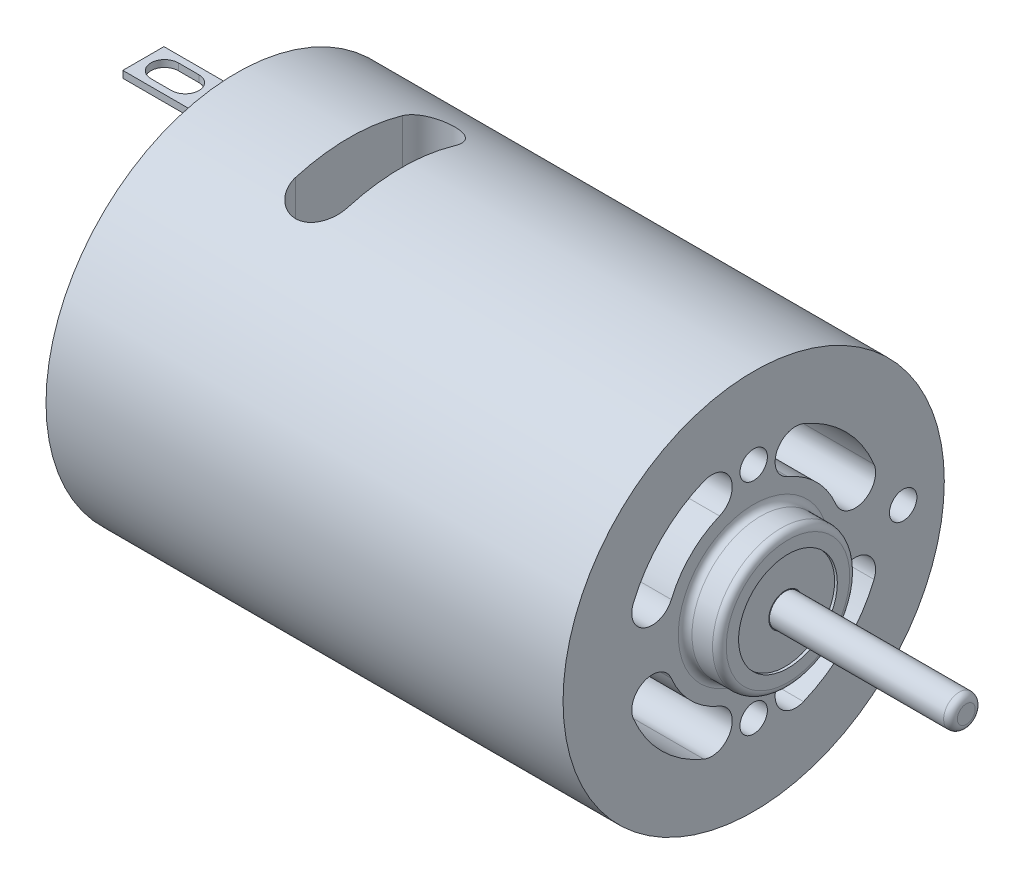
SolidWorks part; units mm, degrees
ref_plane "前视基准面" through (0, 0, 0) normal (0, 0, 1) x (1, 0, 0)
ref_plane "上视基准面" through (0, 0, 0) normal (0, 1, 0) x (1, 0, 0)
ref_plane "右视基准面" through (0, 0, 0) normal (1, 0, 0) x (0, 0, -1)
other "Configuration Table"
sketch "草图1" plane through (0, 0, 0) normal (1, 0, 0) x (0, 0, -1)
  circle A0 centre (0, 0) radius 13.9
  dimension "D1" = 27.8
extrude "凸台-拉伸1" add sketch "草图1" along normal blind 37.7
sketch "草图2" plane through (0, 0, 0) normal (0, 1, 0) x (1, 0, 0)
  line L0 (10.1, 3.9) -> (10.1, -3.9) construction
  line L1 (12, 3.9) -> (12, -3.9)
  line L2 (8.2, 3.9) -> (8.2, -3.9)
  line L3 (0, 13.9) -> (0, -13.9) construction
  line L4 (6.8198, 5.8) -> (14.1425, 5.8) construction
  line L5 (10.1, -5.8) -> (14.1425, -5.8) construction
  line L6 (10.1, 3.9) -> (10.1, -3.9) construction
  line L7 (10.1, 0) -> (12, 0) construction
  line L8 (37.7, 0) -> (0, 0) construction
  arc A0 (12, 3.9) -> (8.2, 3.9) centre (10.1, 3.9) ccw
  arc A1 (8.2, -3.9) -> (12, -3.9) centre (10.1, -3.9) ccw
  point P2 (10.1, 0)
  dimension "D1" = 8.2
  dimension "D2" = 3.8
  dimension "D3" = 11.6
extrude "切除-拉伸1" cut sketch "草图2" against normal through all both and the other way through all
sketch "草图3" plane through (0, 0, 0) normal (-1, 0, 0) x (0, 0, 1)
  line L0 (13.9, 0) -> (13.9, -11.0643) construction
  line L1 (13.7, 0) -> (13.7, -11.0643) construction
  circle A0 centre (0, 0) radius 13.7
  circle A1 centre (0, 0) radius 13.9 construction
  dimension "D1" = 0.2
extrude "切除-拉伸2" cut sketch "草图3" against normal blind 1
sketch "草图6" plane through (1, 0, 0) normal (-1, 0, 0) x (0, 0, 1)
  line L0 (-7.8848, 13.9) -> (16.5622, 13.9) construction
  line L1 (-3.85, -13.1479) -> (3.85, -13.1479)
  line L2 (-3.85, -13.1479) -> (-3.85, 13.1479)
  line L3 (-3.85, 13.1479) -> (3.85, 13.1479)
  line L4 (3.85, -13.1479) -> (3.85, 13.1479)
  line L5 (-3.85, -13.1479) -> (3.85, 13.1479) construction
  line L6 (-3.85, 13.1479) -> (3.85, -13.1479) construction
  line L7 (0, -11.15) -> (0, 11.15) construction
  line L8 (-3.85, -9.1) -> (3.85, -9.1)
  line L9 (-3.85, -9.1) -> (-3.85, 9.1)
  line L10 (-3.85, 9.1) -> (3.85, 9.1)
  line L11 (3.85, -9.1) -> (3.85, 9.1)
  line L12 (-3.85, -9.1) -> (3.85, 9.1) construction
  line L13 (-3.85, 9.1) -> (3.85, -9.1) construction
  line L14 (-1.5, 10.9) -> (1.5, 10.9)
  line L15 (-1.5, 10.9) -> (-1.5, 11.4)
  line L16 (-1.5, 11.4) -> (1.5, 11.4)
  line L17 (1.5, 10.9) -> (1.5, 11.4)
  line L18 (-1.5, 10.9) -> (1.5, 11.4) construction
  line L19 (-1.5, 11.4) -> (1.5, 10.9) construction
  line L20 (-1.5, -11.4) -> (1.5, -11.4)
  line L21 (-1.5, -11.4) -> (-1.5, -10.9)
  line L22 (-1.5, -10.9) -> (1.5, -10.9)
  line L23 (1.5, -11.4) -> (1.5, -10.9)
  line L24 (-1.5, -11.4) -> (1.5, -10.9) construction
  line L25 (-1.5, -10.9) -> (1.5, -11.4) construction
  circle A0 centre (0, 0) radius 13.9 construction
  circle A1 centre (0, 0) radius 13.7 construction
  point P0 (0, 0)
  point P7 (0, 11.15)
  point P13 (0, 0)
  point P22 (0, -11.15)
  circle M11 centre (0, 0) radius 13.7
  dimension "D1" = 7.7
  dimension "D2" = 4.8
  dimension "D3" = 3
  dimension "D4" = 0.5
  dimension "D5" = 3
extrude "凸台-拉伸7" add sketch "草图6" along normal blind 1 contours L2 L10 L4 L3 | L8 L2 L1 L4 | L1 M11 | L3 M11 | L20 L23 L22 L21 | L14 L17 L16 L15 region at (1, -11.124, -3.763) region at (1, -13.3691, 0) region at (1, 13.0609, 0) region at (1, 13.3691, 0) region at (1, 11.15, 0) region at (1, -11.15, 0)
extrude "凸台-拉伸8" add sketch "草图6<4>" along normal blind 6.8 from surface contours L20 L23 L22 L21 | L14 L17 L16 L15 region at (1, 11.15, 0) region at (1, -11.15, 0) starting at face at (0, 0, 0)
sketch "草图6<4>" plane through (1, 0, 0) normal (-1, 0, 0) x (0, 0, 1) same geometry as "草图6"
sketch "草图7" plane through (0, -11.4, 0) normal (0, -1, 0) x (1, 0, 0)
  line L0 (-5.25, 0) -> (-3.75, 0) construction
  line L1 (-5.25, 1) -> (-3.75, 1)
  line L2 (-5.25, -1) -> (-3.75, -1)
  line L3 (-4.5, 1.5) -> (-4.5, -1.5) construction
  line L4 (-6.8, 1.5) -> (0, 1.5) construction
  line L5 (-6.8, -1.5) -> (0, -1.5) construction
  line L6 (-6.8, -1.5) -> (-6.8, 1.5) construction
  arc A0 (-5.25, 1) -> (-5.25, -1) centre (-5.25, 0) ccw
  arc A1 (-3.75, -1) -> (-3.75, 1) centre (-3.75, 0) ccw
  point P3 (-4.5, 0)
  dimension "D1" = 1.5
  dimension "D2" = 1
  dimension "D3" = 2.3
extrude "切除-拉伸4" cut sketch "草图7" against normal through all
sketch "草图4" plane through (1, 0, 0) normal (-1, 0, 0) x (0, 0, 1)
  line L1 (-8.5412, -8.5) -> (8.5412, -8.5)
  line L2 (-8.5412, -8.5) -> (-8.5412, 8.5)
  line L3 (-8.5412, 8.5) -> (8.5412, 8.5)
  line L4 (8.5412, -8.5) -> (8.5412, 8.5)
  line L5 (-8.5412, -8.5) -> (8.5412, 8.5) construction
  line L6 (-8.5412, 8.5) -> (8.5412, -8.5) construction
  circle A0 centre (0, 0) radius 12.05
  point P0 (0, 0)
  dimension "D2" = 24.1
  dimension "D1" = 17
extrude "凸台-拉伸2" add sketch "草图4" along normal blind 1 contours L1 L4 L3 L2 | L2 A0 | L4 A0 region at (1, 0, 0) region at (1, 0, -9.9639) region at (1, 0, 9.9639)
sketch "草图5" plane through (0, 0, 0) normal (-1, 0, 0) x (0, 0, 1)
  circle A0 centre (0, 0) radius 5
  circle A1 centre (0, 0) radius 3
  circle A2 centre (0, 0) radius 1.15
  circle A3 centre (0, 0) radius 2.25
  dimension "D1" = 10
  dimension "D2" = 2.3
  dimension "D3" = 6
  dimension "D4" = 4.5
extrude "凸台-拉伸3" add sketch "草图5" along normal blind 4 contours A2 region at (0, 0, 0)
extrude "凸台-拉伸4" add sketch "草图5<3>" along normal blind 2 contours A0
sketch "草图5<3>" plane through (0, 0, 0) normal (-1, 0, 0) x (0, 0, 1) same geometry as "草图5"
extrude "凸台-拉伸5" add sketch "草图5<4>" along normal blind 3 contours A1
sketch "草图5<4>" plane through (0, 0, 0) normal (-1, 0, 0) x (0, 0, 1) same geometry as "草图5"
extrude "切除-拉伸3" cut sketch "草图5<5>" against normal blind 2 from surface contours A3 A2 region at (0, 0, -2.1864) starting at face at (-3, 0, 1.15)
sketch "草图5<5>" plane through (0, 0, 0) normal (-1, 0, 0) x (0, 0, 1) same geometry as "草图5"
fillet "圆角1" radius 1 1 edges at (-2, 0, 5)
fillet "圆角2" radius 1 1 edges at (-3, 0, 3)
fillet "圆角3" radius 0.5 1 edges at (-4, 0, 1.15)
sketch "草图8" plane through (37.7, 0, 0) normal (1, 0, 0) x (0, 0, -1)
  circle A0 centre (0, 0) radius 1.15
  circle A1 centre (0, 0) radius 3.6
  circle A2 centre (0, 0) radius 5
  circle A3 centre (0, 0) radius 1.2
  dimension "D1" = 2.3
  dimension "D2" = 2.4
  dimension "D3" = 7.2
  dimension "D4" = 10
extrude "凸台-拉伸9" add sketch "草图8" along normal blind 2.5 contours A2 A1 region at (37.7, 0, 4.8586)
extrude "凸台-拉伸10" add sketch "草图8<3>" along normal blind 2.3 contours A1 A3 region at (37.7, 0, 3.4982)
sketch "草图8<3>" plane through (37.7, 0, 0) normal (1, 0, 0) x (0, 0, -1) same geometry as "草图8"
extrude "凸台-拉伸11" add sketch "草图8<4>" along normal blind 13.2 from surface contours A0 region at (37.7, 0, 0) starting at face at (40, 0, -1.2)
sketch "草图8<4>" plane through (37.7, 0, 0) normal (1, 0, 0) x (0, 0, -1) same geometry as "草图8"
fillet "圆角4" radius 0.5 1 edges at (53.2, 0, -1.15)
fillet "圆角5" radius 0.5 1 edges at (40.2, 0, -5)
fillet "圆角6" radius 0.5 1 edges at (37.7, 0, -5)
sketch "草图9" plane through (37.7, 0, 0) normal (1, 0, 0) x (0, 0, -1)
  line L0 (0, 0) -> (29.4829, 0) construction
  line L1 (0, 0) -> (0, 13.0214) construction
  line L2 (0, 0) -> (14.3447, 14.3447) construction
  line L3 (0, 0) -> (-11.9301, 11.9301) construction
  line L4 (-3.0615, 7.391) -> (3.0615, 7.391) construction
  line L5 (3.0615, 7.391) -> (7.391, 3.0615) construction
  line L6 (11.9, 0) -> (11.9, 6.3244) construction
  line L7 (13.9, -3.7057) -> (13.9, 4.9108) construction
  circle A0 centre (0, 0) radius 6.5
  circle A1 centre (0, 0) radius 9.5
  circle A2 centre (0, 0) radius 8 construction
  circle A3 centre (3.0615, 7.391) radius 1.5
  circle A4 centre (7.391, 3.0615) radius 1.5
  circle A5 centre (7.391, -3.0615) radius 1.5
  circle A6 centre (3.0615, -7.391) radius 1.5
  circle A7 centre (-3.0615, -7.391) radius 1.5
  circle A8 centre (-7.391, -3.0615) radius 1.5
  circle A9 centre (-7.391, 3.0615) radius 1.5
  circle A10 centre (-3.0615, 7.391) radius 1.5
  circle A11 centre (0, 8) radius 1
  circle A12 centre (0, -8) radius 1
  circle A13 centre (10.9, 0) radius 1
  circle A17 centre (0, 0) radius 13.9 construction
  dimension "D2" = 19
  dimension "D3" = 16
  dimension "D4" = 2
  dimension "D5" = 2
extrude "切除-拉伸5" cut sketch "草图9" against normal blind 10 contours A10 A1 A9 A0 | A9 | A10 | A3 | A4 A1 A3 A0 | A4 | A5 | A6 A1 A5 A0 | A6 | A7 | A8 A1 A7 A0 | A8 | A12 | A13 | A11 region at (37.7, 5.6844, -5.6844) region at (37.7, 3.0615, -7.391) region at (37.7, -5.6844, -5.6844) region at (37.7, -3.0615, -7.391) region at (37.7, 7.391, -3.0615) region at (37.7, -7.391, -3.0615) region at (37.7, 5.6844, 5.6844) region at (37.7, 7.391, 3.0615) region at (37.7, -5.6844, 5.6844) region at (37.7, -7.391, 3.0615) region at (37.7, 3.0615, 7.391) region at (37.7, -3.0615, 7.391) region at (37.7, -8, 0) region at (37.7, 0, -10.9)
sketch "草图11" plane through (0, 0, 0) normal (-1, 0, 0) x (0, 0, 1)
  line L1 (-7.25, -2.8) -> (7.25, -2.8)
  line L2 (-7.25, -2.8) -> (-7.25, 2.8)
  line L3 (-7.25, 2.8) -> (7.25, 2.8)
  line L4 (7.25, -2.8) -> (7.25, 2.8)
  line L5 (-7.25, -2.8) -> (7.25, 2.8) construction
  line L6 (-7.25, 2.8) -> (7.25, -2.8) construction
  line L7 (-2.8, -7.25) -> (2.8, -7.25)
  line L8 (-2.8, -7.25) -> (-2.8, 7.25)
  line L9 (-2.8, 7.25) -> (2.8, 7.25)
  line L10 (2.8, -7.25) -> (2.8, 7.25)
  line L11 (-2.8, -7.25) -> (2.8, 7.25) construction
  line L12 (-2.8, 7.25) -> (2.8, -7.25) construction
  line L13 (-7.25, -7.25) -> (7.25, -7.25)
  line L14 (-7.25, -7.25) -> (-7.25, 7.25)
  line L15 (-7.25, 7.25) -> (7.25, 7.25)
  line L16 (7.25, -7.25) -> (7.25, 7.25)
  line L17 (-7.25, -7.25) -> (7.25, 7.25) construction
  line L18 (-7.25, 7.25) -> (7.25, -7.25) construction
  circle A0 centre (0, 0) radius 6.5
  point P0 (0, 0)
  point P6 (0, 0)
  point P11 (0, 0)
  dimension "D3" = 13
  dimension "D1" = 5.6
  dimension "D2" = 14.5
extrude "切除-拉伸6" cut sketch "草图11" against normal blind 10 contours A0 L8 L15 L14 L3 | A0 L3 L16 L15 L10 | A0 L10 L13 L16 L1 | A0 L1 L14 L13 L8 region at (0, -5.4736, -5.4736) region at (0, 5.4736, -5.4736) region at (0, -5.4736, 5.4736) region at (0, 5.4736, 5.4736)
chamfer "倒角1" distance 1 angle 45 4 edges at (5, -7.25, -7.25) (5, 7.25, -7.25) (5, -7.25, 7.25) (5, 7.25, 7.25)
